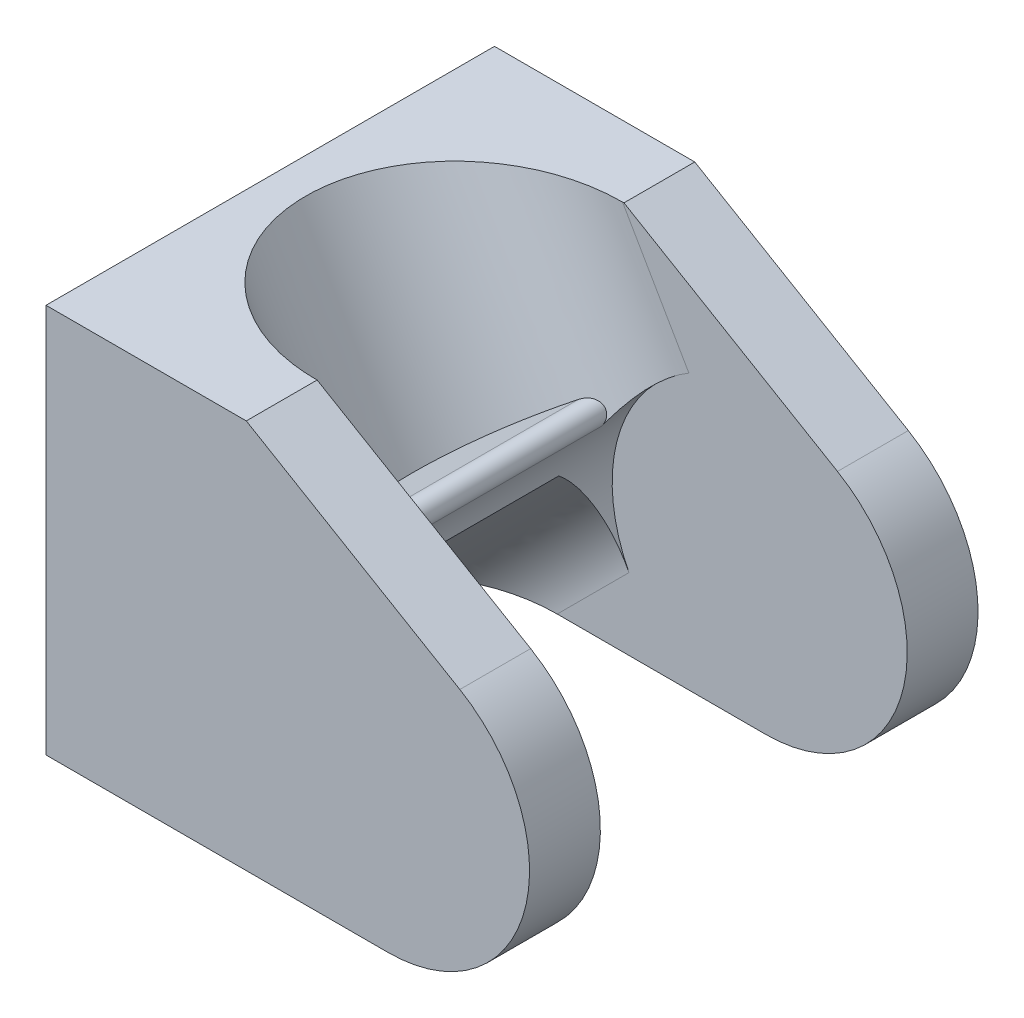
SolidWorks part; units mm, degrees
ref_plane "Спереди" through (0, 0, 0) normal (0, 0, 1) x (1, 0, 0)
ref_plane "Сверху" through (0, 0, 0) normal (0, 1, 0) x (1, 0, 0)
ref_plane "Справа" through (0, 0, 0) normal (1, 0, 0) x (0, 0, -1)
sketch "Эскиз1" plane through (0, 0, 0) normal (0, 0, 1) x (1, 0, 0)
  line L0 (-8.4456, 2.6295) -> (-12.9897, 10.5) construction
  line L1 (-4.2426, 4.2426) -> (-14.4853, -6) construction
  line L2 (-14.4853, -6) -> (0, -6)
  line L3 (0, 0) -> (0, 6) construction
  line L9 (-3.25, 5.6292) -> (-8.4456, 2.6295) construction
  line L11 (0, 6) -> (0, 6.5) construction
  line L14 (-6, 10.5) -> (3.0462, 5.1692)
  line L15 (-14.4853, -6) -> (-14.4853, 10.5)
  line L16 (-14.4853, 10.5) -> (-6, 10.5)
  line L23 (-4.2426, -4.2426) -> (-4.5962, -4.5962) construction
  circle A0 centre (0, 0) radius 5
  circle A1 centre (0, 0) radius 6
  circle A4 centre (0, 0) radius 6.5 construction
  arc A5 (-5.7513, 3.0287) -> (-6.3123, 1.5509) centre (0, 0) ccw
  arc A14 (-6.5025, 3.7513) -> (-5.7513, 3.0287) centre (-6.2313, 3.2815) cw
  arc A16 (-6.3123, 1.5509) -> (-8.9809, -0.4956) centre (0.1088, -9.5852) ccw
sketch "Эскиз2" plane through (0, 0, 0) normal (0, 0, 1) x (1, 0, 0)
  line L0 (3.0462, 5.1692) -> (-6, 10.5)
  line L1 (-6, 10.5) -> (-14.4853, 10.5)
  line L2 (-14.4853, 10.5) -> (-14.4853, -6)
  line L3 (-14.4853, -6) -> (0, -6)
  arc A0 (0, -6) -> (3.0462, 5.1692) centre (0, 0) ccw
extrude "Бобышка-Вытянуть1" add sketch "Эскиз2" along normal mid plane 19
ref_plane "Плоскость1" through (-3.25, 5.6292, 0) normal (-0.5, 0.866, 0) x (0.866, 0.5, 0)
sketch "Эскиз3" plane through (-3.25, 5.6292, 0) normal (-0.5, 0.866, 0) x (0.866, 0.5, 0)
  line L0 (0, 6.5) -> (6, 6.5)
  line L1 (6, -9.5) -> (6, 9.5) construction
  line L2 (6, 6.5) -> (6, -6.5)
  line L3 (6, -6.5) -> (0, -6.5)
  ellipse E0 centre (0, 0) end of major axis (0, 6.5) minor radius 6 (0, 6.5) -> (0, -6.5) ccw
extrude "Вырез-Вытянуть1" cut sketch "Эскиз3" along normal through all both and the other way through all
ref_plane "Плоскость2" through (-4.2426, 4.2426, 0) normal (-0.7071, -0.7071, 0) x (-0.7071, 0.7071, 0)
sketch "Эскиз4" plane through (-4.2426, 4.2426, 0) normal (-0.7071, -0.7071, 0) x (-0.7071, 0.7071, 0)
  line L1 (0, -6.5) -> (-12, -6.5)
  line L2 (0, -6.5) -> (0, 6.5)
  line L3 (0, 6.5) -> (-12, 6.5)
  line L4 (-12, -6.5) -> (-12, 6.5)
  line L5 (0, -6.5) -> (-12, 6.5) construction
  line L6 (0, 6.5) -> (-12, -6.5) construction
  line L8 (0, -6.5) -> (0, -2) construction
  line L9 (0, -2) -> (-4, -2) construction
  line L10 (-6, 0) -> (0, 0) construction
  ellipse E0 centre (-4, -2) end of major axis (-4, -6.5) minor radius 4 (0, -2) -> (-4, -6.5) cw
  ellipse E1 centre (-4, 2) end of major axis (-4, 6.5) minor radius 4 (0, 2) -> (-4, 6.5) ccw
  point P0 (-6, 0)
  point P5 (0, 0)
  point P6 (0, 0)
  point P7 (0, 0)
  point P8 (0, 0)
  point P25 (0, 0)
  point P26 (0, 0)
  point P27 (0, 0)
  point P28 (0, 0)
extrude "Вырез-Вытянуть3" cut sketch "Эскиз4" against normal through all both and the other way through all contours L2 E1 L3 L4 L1 E0 region at (0.1881, -0.1881, 0)
sketch "Эскиз5" plane through (0, 0, 0) normal (0, 0, 1) x (1, 0, 0)
  circle A0 centre (0, 0) radius 6.5
extrude "Вырез-Вытянуть4" cut sketch "Эскиз5" against normal mid plane 13
sketch "Эскиз6" plane through (0, 0, 0) normal (0, 0, 1) x (1, 0, 0)
  line L0 (-6.5025, 3.7513) -> (-8.4456, 2.6295)
  line L1 (-8.4456, 2.6295) -> (-8.9809, -0.4956)
  arc A0 (-8.9809, -0.4956) -> (-6.3123, 1.5509) centre (0.1088, -9.5852) cw
  arc A1 (-5.7513, 3.0287) -> (-6.3123, 1.5509) centre (0, 0) ccw construction
  arc A2 (-6.3123, 1.5509) -> (-5.7513, 3.0287) centre (0, 0) cw
  arc A3 (-5.7513, 3.0287) -> (-6.5025, 3.7513) centre (-6.2313, 3.2815) ccw
  arc A4 (-5.7513, 3.0287) -> (-6.5025, 3.7513) centre (-6.2313, 3.2815) ccw construction
extrude "Бобышка-Вытянуть2" add sketch "Эскиз6" along normal mid plane 13
sketch "Эскиз9" plane through (0, 0, 6.5) normal (0, 0, -1) x (-1, 0, 0)
  line L0 (0, 0) -> (0, 6) construction
  line L1 (0, 0) -> (1.5, 2.5981) construction
  line L2 (1.5, 2.5981) -> (3, 5.1962) construction
  line L3 (3, 5.1962) -> (3.25, 5.6292) construction
  line L4 (6.0622, 10.5) -> (3.25, 5.6292) construction
  line L5 (3.25, 5.6292) -> (10.1378, 1.6525) construction
  line L6 (4.2426, -4.2426) -> (10.1378, 1.6525) construction
  line L7 (0, 0) -> (4.2426, -4.2426) construction
  circle A0 centre (0, 0) radius 6
  arc A1 (0, 3) -> (1.5, 2.5981) centre (0, 0) cw
